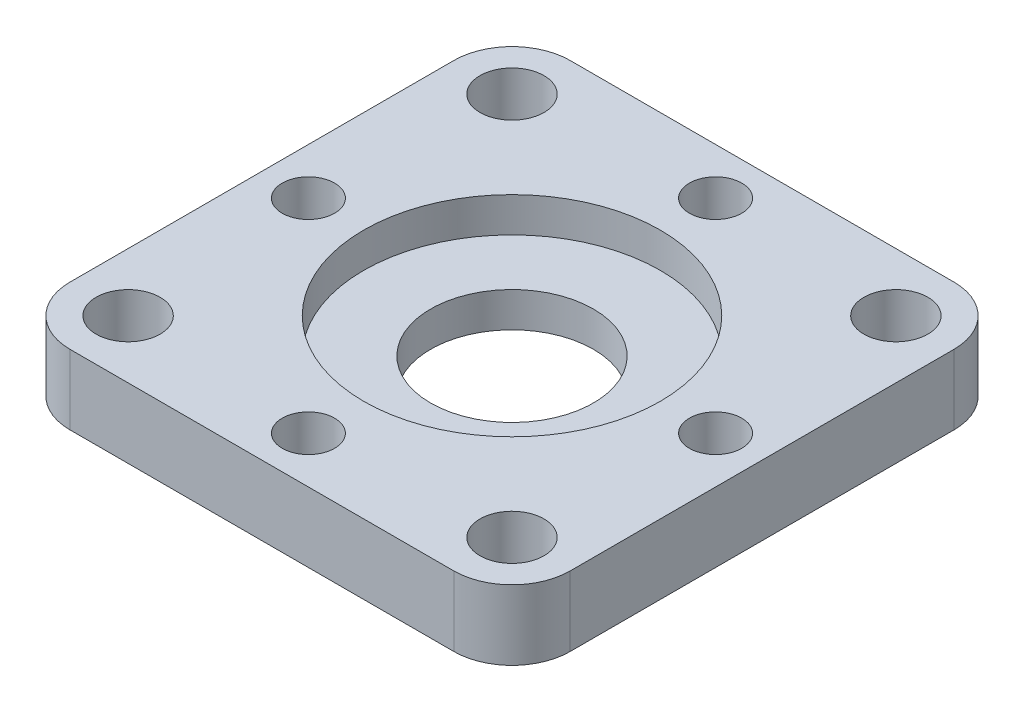
SolidWorks part; units mm, degrees
ref_plane "Front Plane" through (0, 0, 0) normal (0, 0, 1) x (1, 0, 0)
ref_plane "Top Plane" through (0, 0, 0) normal (0, 1, 0) x (1, 0, 0)
ref_plane "Right Plane" through (0, 0, 0) normal (1, 0, 0) x (0, 0, -1)
sketch "Sketch1" plane through (0, 0, 0) normal (0, 1, 0) x (1, 0, 0)
  line L1 (-16.5, -16.5) -> (16.5, -16.5)
  line L2 (-16.5, -16.5) -> (-16.5, 16.5)
  line L3 (-16.5, 16.5) -> (16.5, 16.5)
  line L4 (16.5, -16.5) -> (16.5, 16.5)
  line L5 (-16.5, -16.5) -> (16.5, 16.5) construction
  line L6 (-16.5, 16.5) -> (16.5, -16.5) construction
  line L7 (21.5, -21.5) -> (-21.5, -21.5)
  line L8 (21.5, -21.5) -> (21.5, 21.5)
  line L9 (21.5, 21.5) -> (-21.5, 21.5)
  line L10 (-21.5, -21.5) -> (-21.5, 21.5)
  line L11 (21.5, -21.5) -> (-21.5, 21.5) construction
  line L12 (21.5, 21.5) -> (-21.5, -21.5) construction
  circle A0 centre (-16.5, 16.5) radius 2.75
  circle A1 centre (16.5, 16.5) radius 2.75
  circle A2 centre (-16.5, -16.5) radius 2.75
  circle A3 centre (16.5, -16.5) radius 2.75
  point P0 (0, 0)
  point P10 (0, 0)
  dimension "D3" = 5
  dimension "D1" = 33
  dimension "D2" = 33
  dimension "D4" = 5
extrude "Boss-Extrude1" add sketch "Sketch1" along normal blind 6 contours L10 L7 L8 L9 A3 L1 A2 L2 A0 L3 A1 L4 | A3 L4 A1 L3 A0 L2 A2 L1 region at (0, 0, 0) region at (0, 0, 20.8919)
sketch "Sketch2" plane through (0, 6, 0) normal (0, 1, 0) x (1, 0, 0)
  circle A0 centre (0, 0) radius 7
extrude "Cut-Extrude1" cut sketch "Sketch2" against normal blind 6
sketch "Sketch3" plane through (0, 6, 0) normal (0, 1, 0) x (1, 0, 0)
  circle A0 centre (0, 0) radius 17.5
  circle A1 centre (0, 17.5) radius 2.25
  circle A2 centre (17.5, 0) radius 2.25
  circle A3 centre (0, -17.5) radius 2.25
  circle A4 centre (-17.5, 0) radius 2.25
extrude "Cut-Extrude2" cut sketch "Sketch3" against normal blind 6 contours A0 A1 | A0 A1 | A0 A2 | A0 A2 | A0 A4 | A0 A4 | A0 A3 | A0 A3 region at (16.5195, 6, 0) region at (18.4284, 6, 0) region at (0, 6, -16.5195) region at (0, 6, -18.4284) region at (0, 6, 18.4284) region at (0, 6, 16.5195) region at (-16.5195, 6, 0) region at (-18.4284, 6, 0)
sketch "Sketch4" plane through (0, 6, 0) normal (0, 1, 0) x (1, 0, 0)
  circle A0 centre (0, 0) radius 12.75
extrude "Cut-Extrude3" cut sketch "Sketch4" against normal blind 3
fillet "Fillet1" radius 5 4 edges at (-21.5, 3, 21.5) (21.5, 3, 21.5) (21.5, 3, -21.5) (-21.5, 3, -21.5)
sketch "Sketch5" plane through (0, 6, 0) normal (0, 1, 0) x (1, 0, 0)
  circle A0 centre (0, 0) radius 23.3345
